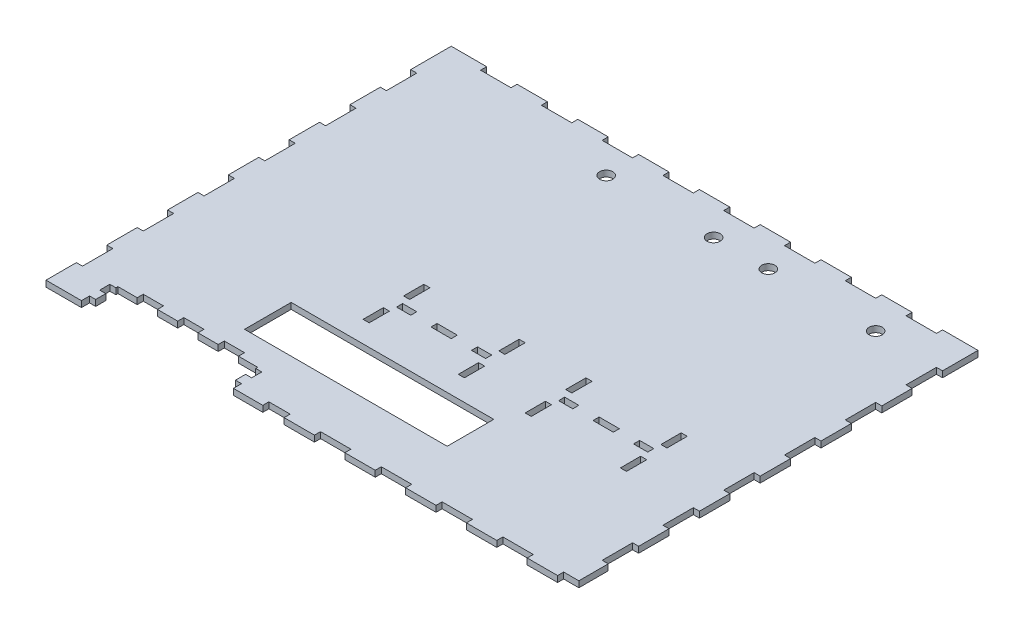
SolidWorks part; units mm, degrees
ref_plane "Alzado" through (0, 0, 0) normal (0, 0, 1) x (1, 0, 0)
ref_plane "Planta" through (0, 0, 0) normal (0, 1, 0) x (1, 0, 0)
ref_plane "Vista lateral" through (0, 0, 0) normal (1, 0, 0) x (0, 0, -1)
sketch "Croquis1" plane through (0, 0, 0) normal (0, 1, 0) x (1, 0, 0)
  line L0 (17.5, 79) -> (20.5, 79)
  line L1 (60, 83) -> (50, 83)
  line L2 (0, 265) -> (17.5, 265)
  line L3 (260, 265) -> (260, 247.5)
  line L4 (252.5, 65) -> (237.5, 65)
  line L5 (50, 83) -> (50, 80)
  line L6 (50, 80) -> (40, 80)
  line L7 (40, 80) -> (40, 83)
  line L8 (84.3736, 80) -> (89.5, 80)
  line L9 (40, 83) -> (30, 83)
  line L10 (17.5, 69) -> (20.5, 69)
  line L11 (0, 65) -> (17.5, 65)
  line L12 (92.5, 69) -> (92.5, 65)
  line L13 (20.5, 74) -> (17.5, 74)
  line L14 (92.5, 69) -> (89.5, 69)
  line L15 (30, 83) -> (30, 80)
  line L16 (89.5, 69) -> (89.5, 74)
  line L17 (92.5, 74) -> (92.5, 79)
  line L18 (115, 143) -> (125, 143)
  line L19 (80, 80) -> (84.3736, 80)
  line L20 (89.5, 80) -> (89.5, 79)
  line L21 (30, 80) -> (25.6264, 80)
  line L22 (115, 140) -> (125, 140)
  line L23 (17.5, 69) -> (17.5, 65)
  line L24 (80, 83) -> (80, 80)
  line L25 (89.5, 74) -> (92.5, 74)
  line L26 (70, 83) -> (80, 83)
  line L27 (120, 93) -> (70, 93)
  line L28 (177.5, 65) -> (177.5, 68)
  line L29 (177.5, 68) -> (162.5, 68)
  line L30 (162.5, 68) -> (162.5, 65)
  line L31 (162.5, 65) -> (147.5, 65)
  line L32 (147.5, 65) -> (147.5, 68)
  line L33 (147.5, 68) -> (132.5, 68)
  line L34 (132.5, 68) -> (132.5, 65)
  line L35 (132.5, 65) -> (117.5, 65)
  line L36 (117.5, 65) -> (117.5, 68)
  line L37 (117.5, 68) -> (107, 68)
  line L38 (107, 68) -> (107, 65)
  line L39 (70, 80) -> (70, 83)
  line L40 (92.5, 65) -> (107, 65)
  line L41 (260, 157.5) -> (257, 157.5)
  line L42 (252.5, 68) -> (260, 68)
  line L43 (252.5, 65) -> (252.5, 68)
  line L44 (237.5, 68) -> (237.5, 65)
  line L45 (222.5, 68) -> (237.5, 68)
  line L46 (222.5, 65) -> (222.5, 68)
  line L47 (207.5, 68) -> (207.5, 65)
  line L48 (192.5, 68) -> (207.5, 68)
  line L49 (192.5, 65) -> (192.5, 68)
  line L50 (257, 157.5) -> (257, 142.5)
  line L51 (257, 142.5) -> (260, 142.5)
  line L52 (260, 142.5) -> (260, 127.5)
  line L53 (260, 127.5) -> (257, 127.5)
  line L54 (257, 127.5) -> (257, 112.5)
  line L55 (257, 112.5) -> (260, 112.5)
  line L56 (260, 112.5) -> (260, 97.5)
  line L57 (260, 97.5) -> (257, 97.5)
  line L58 (257, 97.5) -> (257, 82.5)
  line L59 (257, 82.5) -> (260, 82.5)
  line L60 (89.5, 79) -> (92.5, 79)
  line L61 (257, 247.5) -> (260, 247.5)
  line L62 (257, 232.5) -> (257, 247.5)
  line L63 (260, 232.5) -> (257, 232.5)
  line L64 (257, 217.5) -> (260, 217.5)
  line L65 (257, 202.5) -> (257, 217.5)
  line L66 (260, 202.5) -> (257, 202.5)
  line L67 (257, 187.5) -> (260, 187.5)
  line L68 (257, 172.5) -> (257, 187.5)
  line L69 (260, 172.5) -> (257, 172.5)
  line L70 (137.5, 265) -> (137.5, 262)
  line L71 (137.5, 262) -> (152.5, 262)
  line L72 (152.5, 262) -> (152.5, 265)
  line L73 (152.5, 265) -> (167.5, 265)
  line L74 (167.5, 265) -> (167.5, 262)
  line L75 (167.5, 262) -> (182.5, 262)
  line L76 (182.5, 262) -> (182.5, 265)
  line L77 (182.5, 265) -> (197.5, 265)
  line L78 (197.5, 265) -> (197.5, 262)
  line L79 (197.5, 262) -> (212.5, 262)
  line L80 (212.5, 262) -> (212.5, 265)
  line L81 (212.5, 265) -> (227.5, 265)
  line L82 (227.5, 265) -> (227.5, 262)
  line L83 (227.5, 262) -> (242.5, 262)
  line L84 (242.5, 262) -> (242.5, 265)
  line L85 (17.5, 74) -> (17.5, 79)
  line L86 (17.5, 262) -> (17.5, 265)
  line L87 (32.5, 262) -> (17.5, 262)
  line L88 (32.5, 265) -> (32.5, 262)
  line L89 (47.5, 262) -> (47.5, 265)
  line L90 (62.5, 262) -> (47.5, 262)
  line L91 (62.5, 265) -> (62.5, 262)
  line L92 (77.5, 262) -> (77.5, 265)
  line L93 (92.5, 262) -> (77.5, 262)
  line L94 (92.5, 265) -> (92.5, 262)
  line L95 (107.5, 262) -> (107.5, 265)
  line L96 (122.5, 262) -> (107.5, 262)
  line L97 (122.5, 265) -> (122.5, 262)
  line L98 (0, 140) -> (3, 140)
  line L99 (3, 140) -> (3, 155)
  line L100 (3, 155) -> (0, 155)
  line L101 (0, 155) -> (0, 170)
  line L102 (0, 170) -> (3, 170)
  line L103 (3, 170) -> (3, 185)
  line L104 (3, 185) -> (0, 185)
  line L105 (0, 185) -> (0, 200)
  line L106 (0, 200) -> (3, 200)
  line L107 (3, 200) -> (3, 215)
  line L108 (3, 215) -> (0, 215)
  line L109 (0, 215) -> (0, 230)
  line L110 (0, 230) -> (3, 230)
  line L111 (3, 230) -> (3, 245)
  line L112 (3, 245) -> (0, 245)
  line L113 (20.5, 69) -> (20.5, 74)
  line L114 (60, 80) -> (70, 80)
  line L115 (60, 83) -> (60, 80)
  line L116 (20.5, 79) -> (20.5, 80)
  line L117 (20.5, 80) -> (25.6264, 80)
  line L118 (70, 93) -> (70, 116)
  line L119 (32.5, 265) -> (47.5, 265)
  line L120 (3, 80) -> (0, 80)
  line L121 (3, 95) -> (3, 80)
  line L122 (0, 95) -> (3, 95)
  line L123 (3, 110) -> (0, 110)
  line L124 (3, 125) -> (3, 110)
  line L125 (0, 125) -> (3, 125)
  line L126 (70, 116) -> (170, 116)
  line L127 (170, 116) -> (170, 93)
  line L128 (62.5, 265) -> (77.5, 265)
  line L129 (92.5, 265) -> (107.5, 265)
  line L130 (122.5, 265) -> (137.5, 265)
  line L131 (170, 93) -> (120, 93)
  line L132 (195, 143) -> (205, 143)
  line L133 (98, 156.5) -> (98, 146.5)
  line L134 (242.5, 265) -> (260, 265)
  line L135 (0, 245) -> (0, 265)
  line L136 (98, 136.5) -> (95, 136.5)
  line L137 (95, 136.5) -> (95, 126.5)
  line L138 (95, 126.5) -> (98, 126.5)
  line L139 (0, 125) -> (0, 140)
  line L140 (0, 95) -> (0, 110)
  line L141 (0, 65) -> (0, 80)
  line L143 (105, 140) -> (98, 140)
  line L144 (98, 140) -> (98, 143)
  line L145 (98, 143) -> (105, 143)
  line L146 (105, 143) -> (105, 140)
  line L147 (95, 156.5) -> (98, 156.5)
  line L148 (95, 146.5) -> (95, 156.5)
  line L149 (98, 146.5) -> (95, 146.5)
  line L150 (192.5, 65) -> (177.5, 65)
  line L151 (222.5, 65) -> (207.5, 65)
  line L152 (260, 82.5) -> (260, 68)
  line L153 (142, 146.5) -> (145, 146.5)
  line L154 (145, 146.5) -> (145, 156.5)
  line L155 (260, 172.5) -> (260, 157.5)
  line L156 (260, 202.5) -> (260, 187.5)
  line L157 (260, 232.5) -> (260, 217.5)
  line L158 (145, 156.5) -> (142, 156.5)
  line L159 (98, 126.5) -> (98, 136.5)
  line L161 (142, 156.5) -> (142, 146.5)
  line L162 (142, 126.5) -> (142, 136.5)
  line L163 (145, 126.5) -> (142, 126.5)
  line L164 (145, 136.5) -> (145, 126.5)
  line L165 (142, 136.5) -> (145, 136.5)
  line L166 (178, 156.5) -> (178, 146.5)
  line L167 (175, 156.5) -> (178, 156.5)
  line L168 (135, 143) -> (135, 140)
  line L169 (142, 143) -> (135, 143)
  line L170 (142, 140) -> (142, 143)
  line L171 (135, 140) -> (142, 140)
  line L172 (125, 143) -> (125, 140)
  line L173 (115, 140) -> (115, 143)
  line L174 (185, 140) -> (178, 140)
  line L175 (175, 146.5) -> (175, 156.5)
  line L176 (178, 140) -> (178, 143)
  line L177 (178, 146.5) -> (175, 146.5)
  line L178 (222, 146.5) -> (225, 146.5)
  line L179 (225, 146.5) -> (225, 156.5)
  line L180 (222, 140) -> (222, 143)
  line L181 (225, 156.5) -> (222, 156.5)
  line L182 (222, 156.5) -> (222, 146.5)
  line L183 (178, 136.5) -> (175, 136.5)
  line L184 (175, 136.5) -> (175, 126.5)
  line L185 (178, 143) -> (185, 143)
  line L186 (175, 126.5) -> (178, 126.5)
  line L187 (205, 140) -> (205, 143)
  line L188 (185, 143) -> (185, 140)
  line L189 (178, 126.5) -> (178, 136.5)
  line L190 (222, 126.5) -> (222, 136.5)
  line L191 (225, 126.5) -> (222, 126.5)
  line L192 (225, 136.5) -> (225, 126.5)
  line L193 (222, 136.5) -> (225, 136.5)
  line L195 (215, 143) -> (215, 140)
  line L199 (215, 140) -> (222, 140)
  line L200 (195, 140) -> (205, 140)
  line L204 (222, 143) -> (215, 143)
  line L205 (195, 140) -> (195, 143)
  circle A0 centre (173.5, 248) radius 3.25
  circle A1 centre (93.5, 248) radius 3.25
  circle A2 centre (146.5, 248) radius 3.25
  circle A3 centre (226.5, 248) radius 3.25
  dimension "D6" = 10
  dimension "D14" = 6.5
  dimension "D16" = 6.5
  dimension "D7" = 50
  dimension "D8" = 10
  dimension "D9" = 10
  dimension "D10" = 23
  dimension "D11" = 100
  dimension "D13" = 10
  dimension "D18" = 3
  dimension "D19" = 15
  dimension "D20" = 15
  dimension "D21" = 15
  dimension "D22" = 15
  dimension "D23" = 15
  dimension "D25" = 3
  dimension "D26" = 15
  dimension "D27" = 15
  dimension "D28" = 15
  dimension "D29" = 15
  dimension "D30" = 15
  dimension "D31" = 15
  dimension "D32" = 15
  dimension "D34" = 3
  dimension "D35" = 15
  dimension "D36" = 15
  dimension "D37" = 15
  dimension "D38" = 15
  dimension "D39" = 15
  dimension "D40" = 15
  dimension "D41" = 15
extrude "Saliente-Extruir1" add sketch "Croquis1" along normal blind 3
